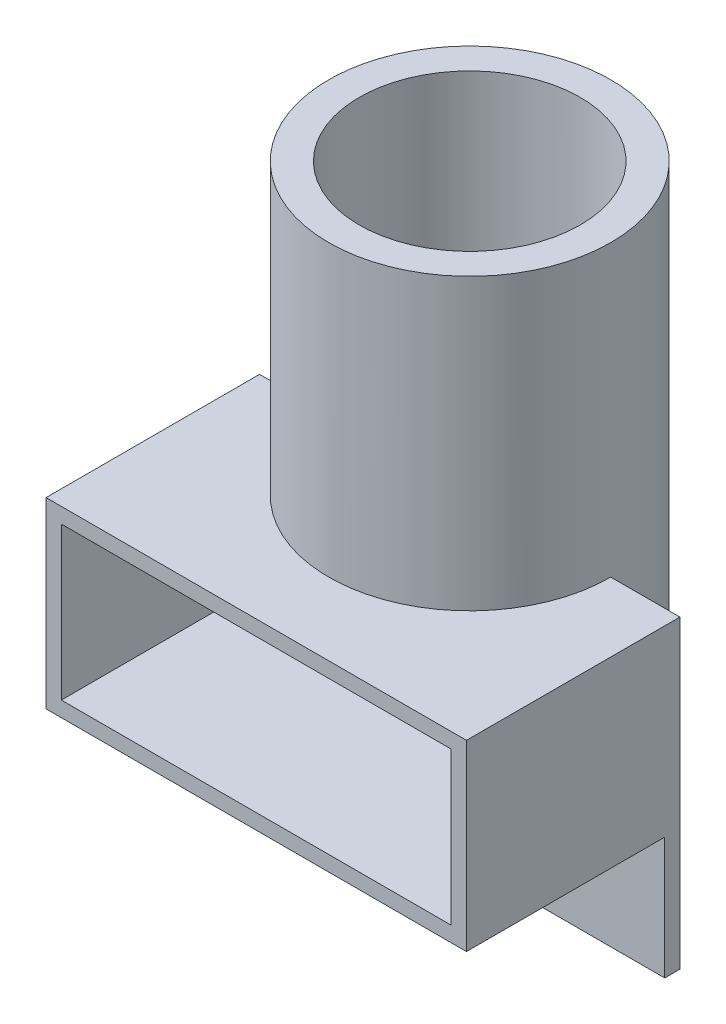
SolidWorks part; units mm, degrees
ref_plane "前基準面" through (0, 0, 0) normal (0, 0, 1) x (1, 0, 0)
ref_plane "上基準面" through (0, 0, 0) normal (0, 1, 0) x (1, 0, 0)
ref_plane "右基準面" through (0, 0, 0) normal (1, 0, 0) x (0, 0, -1)
sketch "刪除圖檔" plane through (0, 0, 0) normal (0, 1, 0) x (1, 0, 0)
  circle A0 centre (0, 0) radius 13.785 construction
  dimension "D1" = 27.57
sketch "草圖2" plane through (0, 0, 0) normal (0, 1, 0) x (1, 0, 0)
  circle A0 centre (0, 0) radius 9.25
  dimension "D1" = 18.5
extrude "19mm" add sketch "草圖2" along normal blind 19 thin thin type one direction reverse wall 2
sketch "草圖14" plane through (0, 0, 0) normal (0, 1, 0) x (1, 0, 0)
  line L0 (-1000, 0) -> (49000, 0) construction
  arc A0 (7.25, 0) -> (-7.25, 0) centre (0, 0) ccw
extrude "伸長-薄件7" add sketch "草圖14" against normal blind 11 thin
sketch "聲音元件" plane through (0, 0, 0) normal (0, 0, 1) x (1, 0, 0)
  line L0 (13.785, 0) -> (-13.785, 0) construction
  line L1 (-13.785, 0) -> (13.785, 0)
  line L2 (-13.785, 0) -> (-13.785, -12)
  line L3 (-13.785, -12) -> (13.785, -12)
  line L4 (13.785, 0) -> (13.785, -12)
  dimension "D1" = 12
extrude "盒子 伸長 " add sketch "聲音元件" along normal blind 14
sketch "草圖6" plane through (0, 0, 14) normal (0, 0, 1) x (1, 0, 0)
  line L0 (-13.785, 0) -> (-13.785, -12) construction
  line L1 (-12.785, -1) -> (12.785, -1)
  line L2 (-12.785, -1) -> (-12.785, -11)
  line L3 (-12.785, -11) -> (12.785, -11)
  line L4 (12.785, -1) -> (12.785, -11)
  line L5 (13.785, -12) -> (13.785, 0) construction
  line L6 (13.785, 0) -> (-13.785, 0) construction
  line L7 (-13.785, -12) -> (13.785, -12) construction
  dimension "D1" = 1
  dimension "D2" = 1
  dimension "D3" = 1
  dimension "D4" = 1
extrude "除料-伸長1" cut sketch "草圖6" against normal blind 12
fillet "圓角1" radius 5 1 edges at (0, 0, 0)
sketch "草圖10" plane through (0, -12, 0) normal (0, -1, 0) x (1, 0, 0)
  line L1 (-13.785, 0) -> (13.785, 0)
  line L2 (-13.785, 0) -> (-13.785, 1)
  line L3 (-13.785, 1) -> (13.785, 1)
  line L4 (13.785, 0) -> (13.785, 1)
  dimension "D1" = 1
extrude "填料-伸長3" add sketch "草圖10" along normal blind 8
